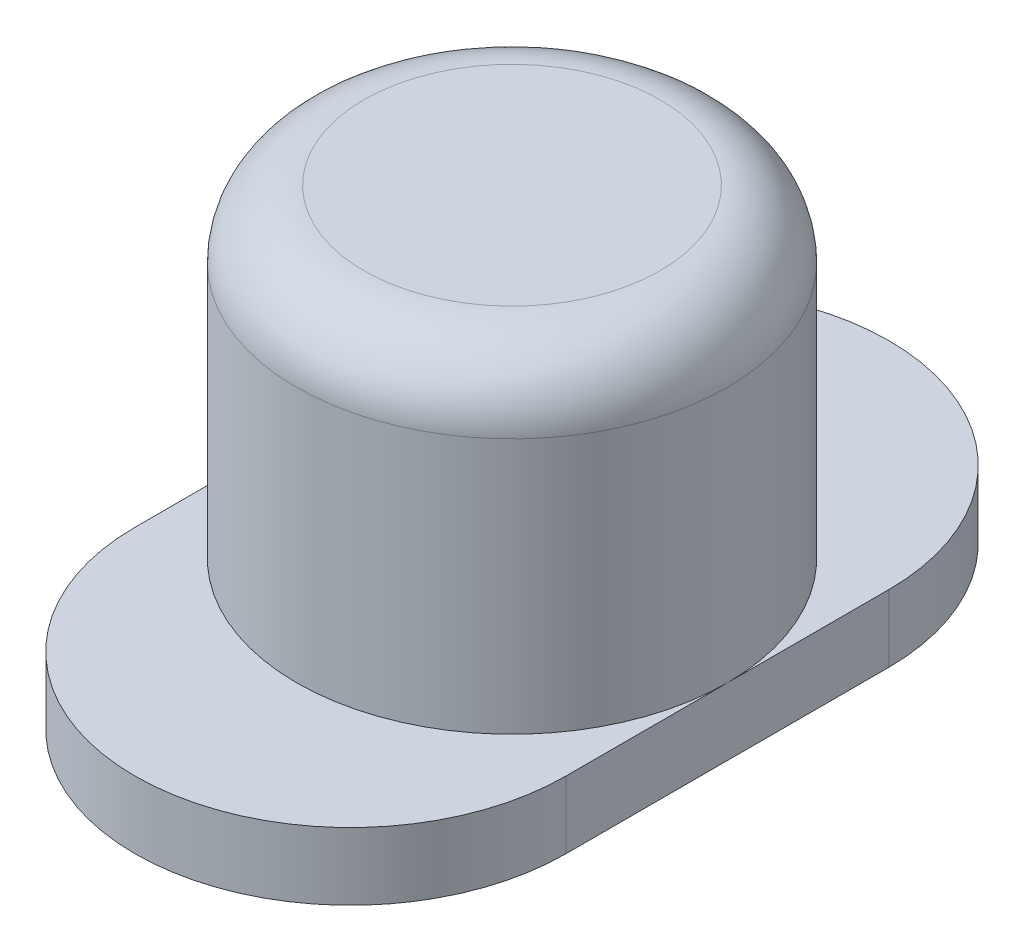
SolidWorks part; units mm, degrees
ref_plane "Front Plane" through (0, 0, 0) normal (0, 0, 1) x (1, 0, 0)
ref_plane "Top Plane" through (0, 0, 0) normal (0, 1, 0) x (1, 0, 0)
ref_plane "Right Plane" through (0, 0, 0) normal (1, 0, 0) x (0, 0, -1)
sketch "Sketch1" plane through (0, 0, 0) normal (0, 0, 1) x (1, 0, 0)
  line L1 (0, 7.25) -> (4, 7.25)
  line L2 (4, 7.25) -> (4, 1.25)
  line L3 (4, 1.25) -> (7, 1.25)
  line L4 (7, 1.25) -> (7, 0)
  line L6 (0, 7.25) -> (0, 6.9292) construction
  line L7 (0, 7.25) -> (0, 0)
  line L10 (0, 0) -> (7, 0)
  dimension "D1" = 4
  dimension "D2" = 3
  dimension "D3" = 6
  dimension "D4" = 1.25
revolve "Revolve1" add sketch "Sketch1" angle 360 about L6
sketch "Sketch2" plane through (0, 0, 0) normal (0, -1, 0) x (1, 0, 0)
  line L1 (-1.75, -1.25) -> (1.75, -1.25)
  line L2 (-1.75, -1.25) -> (-1.75, 1.25)
  line L3 (-1.75, 1.25) -> (1.75, 1.25)
  line L4 (1.75, -1.25) -> (1.75, 1.25)
  line L5 (-1.75, -1.25) -> (1.75, 1.25) construction
  line L6 (-1.75, 1.25) -> (1.75, -1.25) construction
  point P0 (0, 0)
  dimension "D1" = 3.5
  dimension "D2" = 2.5
extrude "Cut-Extrude1" cut sketch "Sketch2" against normal blind 3.5 contours L3 L4 L1 L2
fillet "Fillet1" radius 1.25 1 edges at (-4, 7.25, 0)
sketch "Sketch3" plane through (0, 0, 0) normal (0, 1, 0) x (1, 0, 0)
  line L0 (0, -3) -> (0, 3) construction
  line L1 (-4, -3) -> (-4, 3)
  line L2 (4, -3) -> (4, 3)
  line L3 (0, 3) -> (0, 7) construction
  line L4 (-14, -3) -> (-14, 3)
  line L5 (14, -3) -> (14, 3)
  arc A1 (-4, -3) -> (4, -3) centre (0, -3) ccw
  arc A2 (4, 3) -> (-4, 3) centre (0, 3) ccw
  circle A3 centre (0, 0) radius 7 construction
  circle A4 centre (0, 0) radius 4 construction
  arc A5 (14, 3) -> (-14, 3) centre (0, 3) ccw
  arc A6 (-14, -3) -> (14, -3) centre (0, -3) ccw
  point P5 (0, 0)
  dimension "D1" = 10
extrude "Cut-Extrude2" cut sketch "Sketch3" along normal through all
